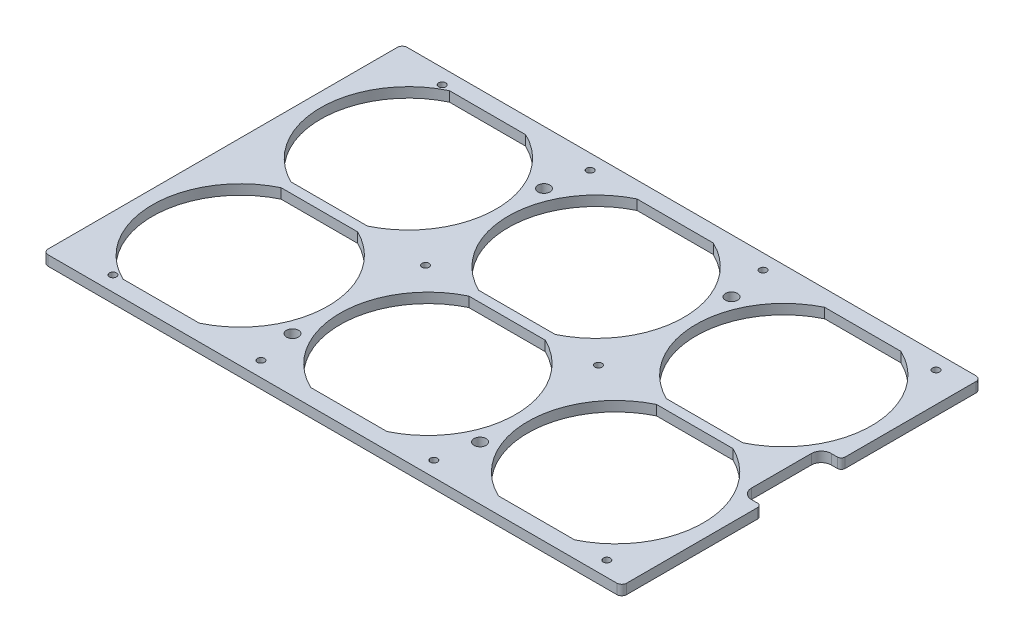
SolidWorks part; units mm, degrees
material "NEOPRENE"
ref_plane "Front" through (0, 0, 0) normal (0, 0, 1) x (1, 0, 0)
ref_plane "Top" through (0, 0, 0) normal (0, 1, 0) x (1, 0, 0)
ref_plane "Right" through (0, 0, 0) normal (1, 0, 0) x (0, 0, -1)
sketch "Sketch1" plane through (0, 0, 0) normal (0, 1, 0) x (1, 0, 0)
  line L0 (-24.3078, -3.1623) -> (24.3078, -3.1623)
  line L1 (-180.975, 114.3) -> (180.975, 114.3)
  line L2 (-184.15, 111.125) -> (-184.15, -111.125)
  line L3 (-180.975, -114.3) -> (180.975, -114.3)
  line L4 (184.15, 111.125) -> (184.15, -111.125)
  line L5 (-184.15, 114.3) -> (184.15, -114.3) construction
  line L6 (-184.15, -114.3) -> (184.15, 114.3) construction
  line L7 (95.1365, -3.1623) -> (143.7521, -3.1623)
  line L8 (95.1365, -3.1623) -> (95.1365, -103.8733) construction
  line L9 (95.1365, -103.8733) -> (143.7521, -103.8733)
  line L10 (143.7521, -3.1623) -> (143.7521, -103.8733) construction
  line L11 (95.1365, -3.1623) -> (143.7521, -103.8733) construction
  line L12 (95.1365, -103.8733) -> (143.7521, -3.1623) construction
  line L13 (-24.3078, -103.8733) -> (24.3078, -103.8733)
  line L14 (-143.7521, -3.1623) -> (-95.1365, -3.1623)
  line L15 (-143.7521, -103.8733) -> (-95.1365, -103.8733)
  line L16 (-24.3078, 103.8733) -> (24.3078, 103.8733)
  line L17 (-24.3078, 3.1623) -> (24.3078, 3.1623)
  line L18 (-143.7521, 103.8733) -> (-95.1365, 103.8733)
  line L19 (-143.7521, 3.1623) -> (-95.1365, 3.1623)
  line L20 (95.1365, 103.8733) -> (143.7521, 103.8733)
  line L21 (95.1365, 3.1623) -> (143.7521, 3.1623)
  line L22 (-95.1365, -103.8733) -> (-24.3078, -103.8733) construction
  line L23 (24.3078, -103.8733) -> (95.1365, -103.8733) construction
  line L24 (119.5086, 53.5178) -> (119.5086, -53.5178) construction
  line L25 (24.3078, 3.1623) -> (24.3078, -3.1623) construction
  line L26 (-175.3235, -53.5178) -> (-184.15, -53.5178) construction
  line L27 (175.3235, -53.5178) -> (184.15, -53.5178) construction
  line L28 (-24.3078, -103.8733) -> (-24.3078, -114.3) construction
  line L29 (-24.3078, 103.8733) -> (-24.3078, 114.3) construction
  arc A0 (95.1365, -3.1623) -> (95.1365, -103.8733) centre (119.5086, -53.5178) ccw
  arc A1 (143.7521, -3.1623) -> (143.7521, -103.8733) centre (119.38, -53.5178) cw
  arc A2 (-184.15, -111.125) -> (-180.975, -114.3) centre (-180.975, -111.125) ccw
  arc A3 (184.15, -111.125) -> (180.975, -114.3) centre (180.975, -111.125) cw
  arc A4 (184.15, 111.125) -> (180.975, 114.3) centre (180.975, 111.125) ccw
  arc A5 (-180.975, 114.3) -> (-184.15, 111.125) centre (-180.975, 111.125) ccw
  circle A6 centre (-149.225, -104.775) radius 2.2479 construction
  circle A8 centre (-55.0333, -104.775) radius 2.2479 construction
  arc A10 (-24.3078, -3.1623) -> (-24.3078, -103.8733) centre (0.0643, -53.5178) ccw
  arc A11 (24.3078, -3.1623) -> (24.3078, -103.8733) centre (-0.0643, -53.5178) cw
  arc A12 (-143.7521, -3.1623) -> (-143.7521, -103.8733) centre (-119.38, -53.5178) ccw
  arc A13 (-95.1365, -3.1623) -> (-95.1365, -103.8733) centre (-119.5086, -53.5178) cw
  arc A14 (-24.3078, 103.8733) -> (-24.3078, 3.1623) centre (0.0643, 53.5178) ccw
  arc A15 (24.3078, 103.8733) -> (24.3078, 3.1623) centre (-0.0643, 53.5178) cw
  arc A16 (-143.7521, 103.8733) -> (-143.7521, 3.1623) centre (-119.38, 53.5178) ccw
  arc A17 (-95.1365, 103.8733) -> (-95.1365, 3.1623) centre (-119.5086, 53.5178) cw
  arc A18 (95.1365, 103.8733) -> (95.1365, 3.1623) centre (119.5086, 53.5178) ccw
  arc A19 (143.7521, 103.8733) -> (143.7521, 3.1623) centre (119.38, 53.5178) cw
  circle A20 centre (55.0333, -104.775) radius 2.2479 construction
  circle A21 centre (165.1, -104.775) radius 2.2479 construction
  circle A22 centre (165.1, 104.775) radius 2.2479 construction
  circle A23 centre (55.0333, 104.775) radius 2.2479 construction
  circle A24 centre (-55.0333, 104.775) radius 2.2479 construction
  circle A25 centre (-149.225, 104.775) radius 2.2479 construction
  circle A26 centre (-149.225, -104.775) radius 2.2479
  circle A27 centre (-55.0333, -104.775) radius 2.2479
  circle A28 centre (55.0333, -104.775) radius 2.2479
  circle A29 centre (165.1, -104.775) radius 2.2479
  circle A30 centre (165.1, 104.775) radius 2.2479
  circle A31 centre (55.0333, 104.775) radius 2.2479
  circle A32 centre (-55.0333, 104.775) radius 2.2479
  circle A33 centre (-149.225, 104.775) radius 2.2479
  circle A34 centre (59.69, 80.01) radius 1.8288 construction
  circle A35 centre (-59.69, 80.01) radius 1.8288 construction
  circle A36 centre (-55.0333, 0) radius 2.2479 construction
  circle A37 centre (55.0333, 0) radius 2.2479 construction
  circle A38 centre (59.69, -80.01) radius 1.8288 construction
  circle A39 centre (-59.69, -80.01) radius 1.8288 construction
  circle A40 centre (59.69, 80.01) radius 1.8288 construction
  circle A41 centre (-59.69, 80.01) radius 1.8288 construction
  circle A42 centre (-55.0333, 0) radius 2.2479
  circle A43 centre (55.0333, 0) radius 2.2479
  circle A44 centre (59.69, -80.01) radius 1.8288 construction
  circle A45 centre (-59.69, -80.01) radius 1.8288 construction
  circle A46 centre (-59.69, 80.01) radius 3.81
  circle A47 centre (-59.69, -80.01) radius 3.81
  circle A48 centre (59.69, -80.01) radius 3.81
  circle A49 centre (59.69, 80.01) radius 3.81
  point P0 (0, 0)
  point P6 (119.4443, -53.5178)
  dimension "D4" = 111.887
  dimension "D8" = 3.175
  dimension "D9" = 7.62
  dimension "D1" = 368.3
  dimension "D2" = 228.6
  dimension "D3" = 100.711
  dimension "D5" = 48.6156
  dimension "D6" = 119.38
  dimension "D7" = 107.0356
  dimension "D11" = 3
  dimension "D12" = 2
extrude "Boss-Extrude1" add sketch "Sketch1" along normal blind 6.35
sketch "Sketch2" plane through (0, 6.35, 0) normal (0, 1, 0) x (1, 0, 0)
  line L0 (0, 0) -> (184.15, 0) construction
  line L1 (184.15, -111.125) -> (184.15, 111.125) construction
  line L2 (184.15, -111.125) -> (184.15, 111.125) construction
  line L3 (184.15, 25.4) -> (177.8, 25.4)
  line L4 (184.15, 25.4) -> (184.15, -25.4)
  line L5 (184.15, -25.4) -> (177.8, -25.4)
  line L6 (171.45, 19.05) -> (171.45, -19.05)
  arc A0 (177.8, -25.4) -> (171.45, -19.05) centre (177.8, -19.05) cw
  arc A1 (177.8, 25.4) -> (171.45, 19.05) centre (177.8, 19.05) ccw
  point P14 (171.45, -25.4)
  point P17 (171.45, 25.4)
  dimension "D3" = 6.35
  dimension "D1" = 12.7
  dimension "D2" = 50.8
extrude "Cut-Extrude1" cut sketch "Sketch2" against normal through all and the other way through all
fillet "Fillet1" radius 2.54 2 edges at (184.15, 3.175, 25.4) (184.15, 3.175, -25.4)
